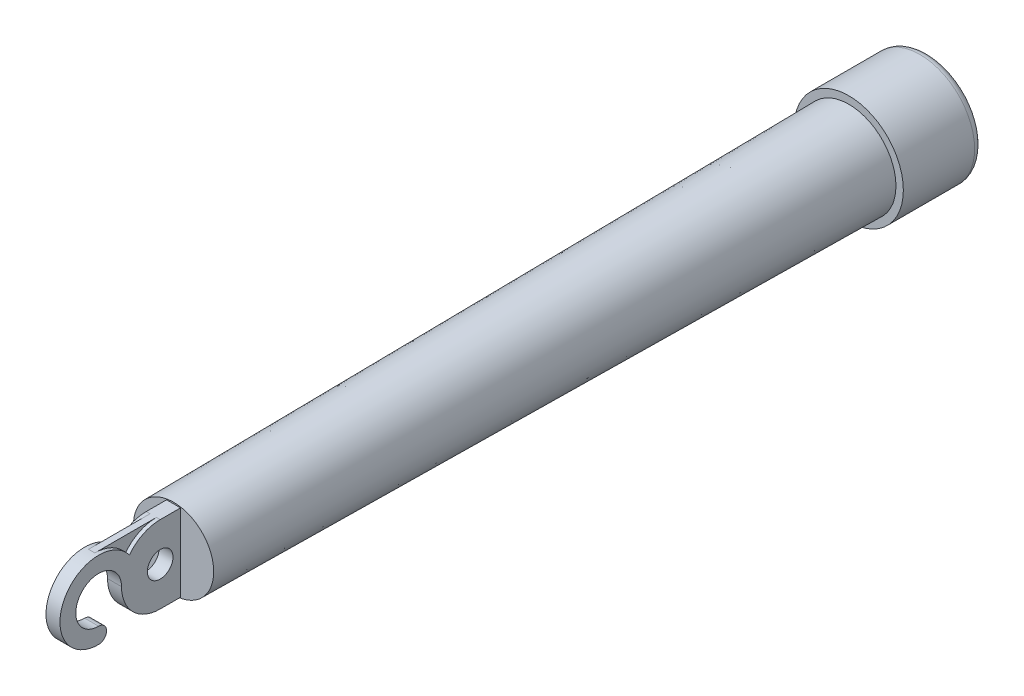
SolidWorks part; units mm, degrees
ref_plane "Front Plane" through (0, 0, 0) normal (0, 0, 1) x (1, 0, 0)
ref_plane "Top Plane" through (0, 0, 0) normal (0, 1, 0) x (1, 0, 0)
ref_plane "Right Plane" through (0, 0, 0) normal (1, 0, 0) x (0, 0, -1)
sketch "Sketch1" plane through (0, 0, 0) normal (0, 0, 1) x (1, 0, 0)
  circle A0 centre (0, 0) radius 9.375
  dimension "D1" = 18.75
extrude "End Cap Main" add sketch "Sketch1" along normal blind 13.65
fillet "Fillet1" radius 1.4 1 edges at (9.375, 0, 0)
sketch "Sketch2" plane through (0, 0, 0) normal (0, 0, -1) x (-1, 0, 0)
  circle A0 centre (0, 0) radius 4.4
extrude "End Cap cut" cut sketch "Sketch2" against normal blind 9.3
fillet "Fillet2" radius 1 1 edges at (-4.4, 0, 0)
sketch "Sketch16" plane through (0, 0, 13.65) normal (0, 0, 1) x (1, 0, 0)
  circle A0 centre (0, 0) radius 8.105
extrude "Cut-Extrude12" cut sketch "Sketch16" against normal blind 2.5
ref_plane "Plane1" through (0, 0, 129.67) normal (0, 0, 1) x (1, 0, 0)
sketch "Sketch5" plane through (0, 0, 13.65) normal (0, 0, 1) x (1, 0, 0)
  circle A0 centre (0, 0) radius 8.105
  dimension "D1" = 16.21
extrude "Boss-Extrude4" add sketch "Sketch5<3>" against normal blind 2.5
sketch "Sketch5<3>" plane through (0, 0, 13.65) normal (0, 0, 1) x (1, 0, 0) same geometry as "Sketch5"
sketch "Sketch4" plane through (0, 0, 129.67) normal (0, 0, 1) x (1, 0, 0)
  circle A0 centre (0, 0) radius 6.9
  dimension "D1" = 13.8
loft "Loft1" add profiles "Sketch4", "Sketch5" connector at (6.9, 0, 129.67) connector at (8.105, 0, 13.65)
sketch "Sketch6" plane through (0, 0, 129.67) normal (0, 0, 1) x (1, 0, 0)
  line L1 (-1.2, -6.65) -> (1.2, -6.65)
  line L2 (-1.2, -6.65) -> (-1.2, 6.65)
  line L3 (-1.2, 6.65) -> (1.2, 6.65)
  line L4 (1.2, -6.65) -> (1.2, 6.65)
  line L5 (-1.2, -6.65) -> (1.2, 6.65) construction
  line L6 (-1.2, 6.65) -> (1.2, -6.65) construction
  point P0 (0, 0)
  dimension "D1" = 13.3
  dimension "D2" = 2.4
extrude "Boss-Extrude2" add sketch "Sketch6" along normal blind 20.72
sketch "Sketch8" plane through (1.2, 0, 0) normal (1, 0, 0) x (0, 0, -1)
  line L0 (-129.67, 6.65) -> (-129.67, -6.6147)
  line L1 (-150.39, 6.65) -> (-129.67, 6.65) construction
  line L2 (-129.67, 10.3125) -> (-129.67, -10.3125) construction
  line L3 (-133.1643, 6.65) -> (-129.67, 6.65)
  line L4 (-133.1643, -6.65) -> (-129.67, -6.6147)
  line L5 (-150.3893, 0) -> (-150.39, 6.65)
  line L6 (-150.39, 6.65) -> (-143.7393, 6.65)
  circle A0 centre (-143.7393, 0) radius 3.925
  arc A1 (-133.1643, 6.65) -> (-133.0299, -6.6486) centre (-133.1643, 0) ccw
  circle A2 centre (-143.7393, 0) radius 6.65
  dimension "D1" = 7.85
  dimension "D2" = 13.3
  dimension "D3" = 14.0693
sketch "Sketch9" plane through (1.2, 0, 0) normal (1, 0, 0) x (0, 0, -1)
  line L0 (-150.39, 6.65) -> (-150.39, -6.65)
  line L1 (-150.39, -6.65) -> (-143.7393, -6.65)
  line L2 (-150.39, -6.65) -> (-129.67, -6.65) construction
  line L3 (-150.39, 6.65) -> (-143.7393, 6.65)
  circle A0 centre (-143.7393, 0) radius 6.65 construction
  arc A1 (-143.7393, 6.65) -> (-143.7393, -6.65) centre (-143.7393, 0) ccw
extrude "Cut-Extrude2" cut sketch "Sketch9" against normal up to next
sketch "Sketch10" plane through (1.2, 0, 0) normal (1, 0, 0) x (0, 0, -1)
  line L0 (-143.7393, 6.65) -> (-133.1643, 6.65)
  arc A0 (-138.4518, 4.033) -> (-133.1643, 6.65) centre (-133.1643, 0) cw
  arc A1 (-133.1643, 6.65) -> (-133.0299, -6.6486) centre (-133.1643, 0) ccw construction
  arc A3 (-143.7393, 6.65) -> (-138.4518, 4.033) centre (-143.7393, 0) cw
extrude "Cut-Extrude4" cut sketch "Sketch10" against normal blind 0.655
mirror "Mirror1" about plane through (0, 0, 0) normal (1, 0, 0) of "Cut-Extrude4"
sketch "Sketch12" plane through (1.2, 0, 0) normal (1, 0, 0) x (0, 0, -1)
  line L0 (-143.7393, -3.925) -> (-143.7393, -6.65)
  line L1 (-143.7393, -6.65) -> (-139.8143, -6.65)
  line L2 (-143.7393, -6.65) -> (-129.67, -6.65) construction
  line L3 (-139.8143, -6.65) -> (-139.8143, 0)
  arc A0 (-139.8143, 0) -> (-143.7393, -3.925) centre (-143.7393, 0) ccw
  circle A1 centre (-143.7393, 0) radius 3.925 construction
extrude "Cut-Extrude9" cut sketch "Sketch12" against normal up to next
sketch "Sketch13" plane through (1.2, 0, 0) normal (1, 0, 0) x (0, 0, -1)
  line L0 (-139.8143, 0) -> (-139.8143, -6.65)
  line L1 (-139.8143, -6.65) -> (-133.1643, -6.65)
  arc A0 (-133.1643, -6.65) -> (-139.8143, 0) centre (-133.1643, 0) cw
  circle A1 centre (-143.7393, 0) radius 3.925 construction
extrude "Cut-Extrude10" cut sketch "Sketch13" against normal up to next
sketch "Sketch14" plane through (1.2, 0, 0) normal (1, 0, 0) x (0, 0, -1)
  line L0 (-143.7393, -3.925) -> (-143.7393, -6.65) construction
  line L1 (-143.7393, -3.925) -> (-143.7393, -6.65)
  arc A0 (-143.7393, -6.65) -> (-143.7393, -3.925) centre (-143.7393, -5.2875) ccw
extrude "Boss-Extrude3" add sketch "Sketch14" against normal up to surface (2.4 mm away) up to face at (-1.2, 0.2119, 138.3047)
sketch "Sketch15" plane through (1.2, 0, 0) normal (1, 0, 0) x (0, 0, -1)
  circle A0 centre (-133.1643, 0) radius 2.2
  dimension "D1" = 4.4
extrude "Cut-Extrude11" cut sketch "Sketch15" against normal up to next
